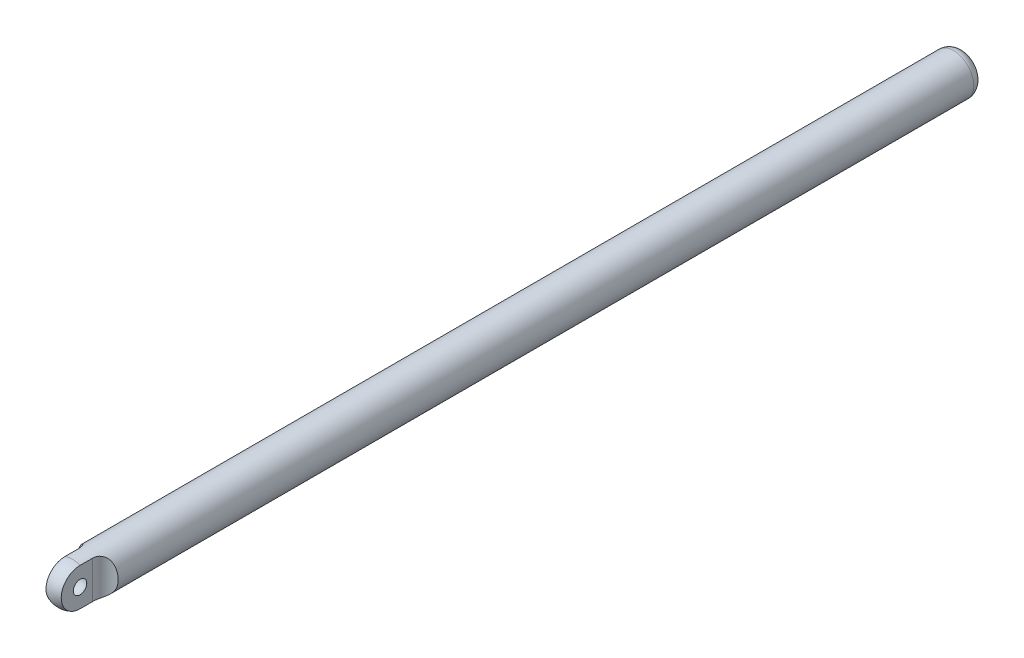
SolidWorks part; units mm, degrees
material "Lega 1345"
ref_plane "Piano frontale" through (0, 0, 0) normal (0, 0, 1) x (1, 0, 0)
ref_plane "Piano superiore" through (0, 0, 0) normal (0, 1, 0) x (1, 0, 0)
ref_plane "Piano destro" through (0, 0, 0) normal (1, 0, 0) x (0, 0, -1)
sketch "Schizzo1" plane through (0, 0, 0) normal (0, 0, 1) x (1, 0, 0)
  circle A0 centre (0, 0) radius 8
extrude "Estrusione-Estrusione1" add sketch "Schizzo1" along normal blind 351.1
sketch "Schizzo2" plane through (0, 0, 0) normal (0, 1, 0) x (1, 0, 0)
  line L0 (4, -1) -> (-4, -1) construction
  line L1 (4, -1) -> (-4, -1)
  arc A0 (4, -1) -> (-4, -1) centre (0, -1) cw
  dimension "D1" = 8
  dimension "D2" = 4
revolve "Rivoluzione1" add sketch "Schizzo2" angle 360 about L0
combine bodies "Abbina1" operation type subtract main body 101 bodies to subtract 102
fillet "Raccordo3" radius 4 1 edges at (8, 0, 0)
sketch "Schizzo5" plane through (0, 0, 351.1) normal (0, 0, 1) x (1, 0, 0)
  line L0 (1.4796, -7.862) -> (-1.4796, 7.862)
  arc A0 (-1.4796, 7.862) -> (1.4796, -7.862) centre (0, 0) cw
  circle A1 centre (0, 0) radius 8 construction
revolve "Rivoluzione4" add sketch "Schizzo5" angle 180 about L0 reverse direction yes
ref_plane "Piano1" through (0, 0, 351.1) normal (0, 0, 1) x (1, 0, 0)
sketch "Schizzo7" plane through (0, 0, 0) normal (0, 1, 0) x (1, 0, 0)
  line L1 (-8, -361.1) -> (-3, -361.1)
  line L2 (-8, -361.1) -> (-8, -341.1)
  line L3 (-8, -341.1) -> (-3, -341.1)
  line L4 (-3, -361.1) -> (-3, -341.1)
  line L5 (8, -351.1) -> (-8, -351.1) construction
  dimension "D1" = 20
  dimension "D2" = 10
  dimension "D3" = 5
extrude "Taglio-Estrusione2" cut sketch "Schizzo7" against normal through all and the other way through all contours L1 L4 L3 L2
mirror "Specchia2" about plane through (0, 0, 0) normal (1, 0, 0) of "Taglio-Estrusione2"
sketch "Schizzo8" plane through (0, 0, 351.1) normal (0, 0, 1) x (1, 0, 0)
  line L0 (4, 0) -> (-4, 0)
  arc A0 (4, 0) -> (-4, 0) centre (0, 0) ccw
  dimension "D1" = 8
revolve "Rivoluzione6" add sketch "Schizzo8" angle 360 about L0
combine bodies "Abbina2" operation type subtract main body 114 bodies to subtract 115
fillet "Raccordo4" radius 5 2 edges at (3, 0, 341.1) (-3, 0, 341.1)
